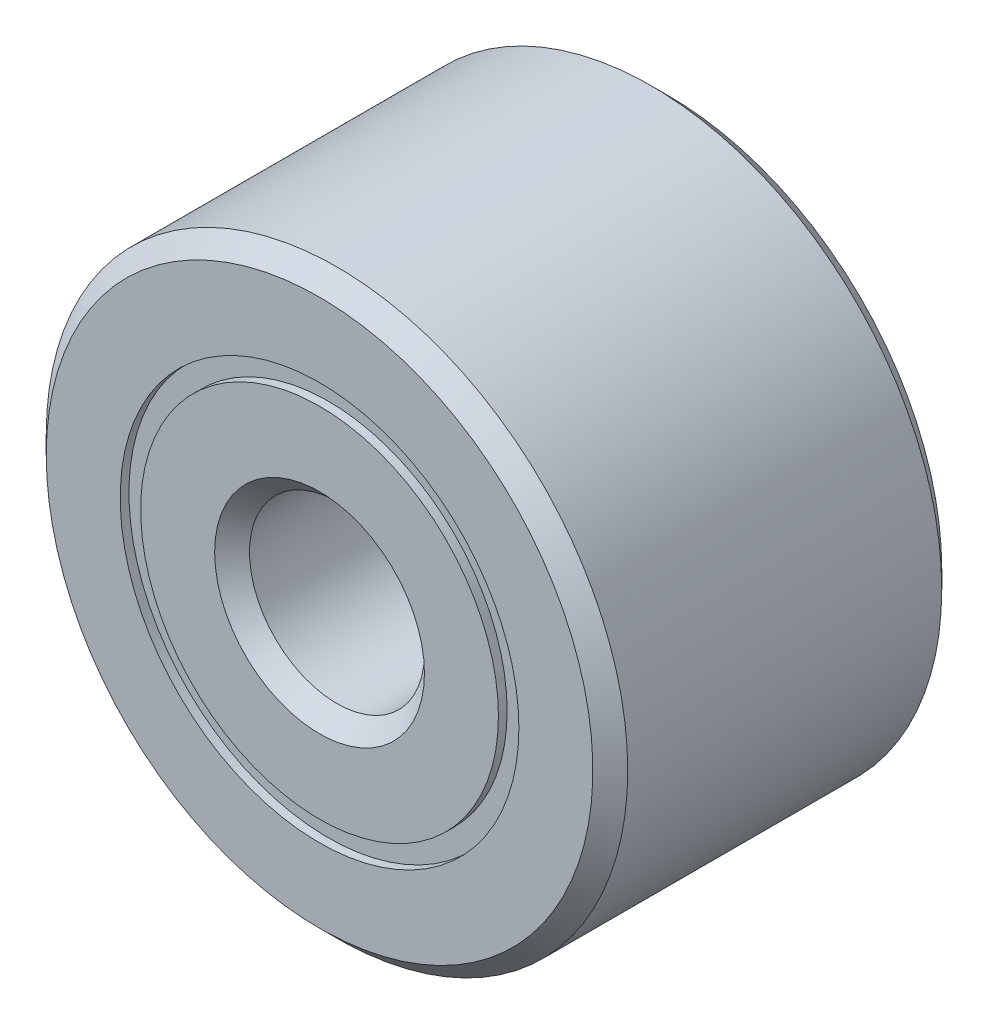
SolidWorks part; units mm, degrees
material "A-Glass Fiber"
ref_plane "Front Plane" through (0, 0, 0) normal (0, 0, 1) x (1, 0, 0)
ref_plane "Top Plane" through (0, 0, 0) normal (0, 1, 0) x (1, 0, 0)
ref_plane "Right Plane" through (0, 0, 0) normal (1, 0, 0) x (0, 0, -1)
sketch "Sketch1" plane through (0, 0, 0) normal (1, 0, 0) x (0, 0, -1)
  line L0 (-1.1906, 0) -> (1.1906, 0) construction
  line L1 (0, 1.9844) -> (0, -1.9844) construction
  line L2 (1.0716, 1.9844) -> (-1.0716, 1.9844)
  line L3 (-1.0716, 1.9844) -> (-1.1906, 1.8653)
  line L4 (-1.1906, 1.8653) -> (-1.1906, 1.3604)
  line L5 (-1.1906, 1.3604) -> (-0.5292, 1.3604)
  line L6 (1.1906, 1.3604) -> (0.5292, 1.3604)
  line L7 (1.1906, 1.8653) -> (1.1906, 1.3604)
  line L8 (1.0716, 1.9844) -> (1.1906, 1.8653)
  line L9 (0, 1.9844) -> (0, 1.2906) construction
  line L10 (0, 1.2906) -> (0, 0.5969) construction
  arc A0 (-0.5292, 1.3604) -> (0.5292, 1.3604) centre (0, 1.2906) cw
  point P14 (0, 0.5969)
  dimension "Width" = 2.3813
  dimension "OD" = 3.9688
  dimension "D1" = 45
  dimension "D2" = 0.1191
  dimension "D3" = 1.0583
  dimension "D4" = 0.0698
revolve "Revolve1" add sketch "Sketch1" angle 360 about L0
sketch "Sketch3" plane through (0, 0, 0) normal (1, 0, 0) x (0, 0, -1)
  line L0 (-0.5292, 1.2209) -> (-1.1906, 1.2209)
  line L1 (-1.1906, 1.8653) -> (-1.1906, 1.3604) construction
  line L2 (-1.0716, 1.9844) -> (-1.1906, 1.8653) construction
  line L3 (-1.1906, 1.2209) -> (-1.1906, 0.716)
  line L5 (-1.1906, 0.716) -> (-1.0716, 0.5969)
  line L6 (-1.0716, 0.5969) -> (1.0716, 0.5969)
  line L7 (1.0716, 1.9844) -> (1.0716, -1.9844) construction
  line L8 (1.0716, 0.5969) -> (1.1906, 0.716)
  line L9 (1.1906, -1.8653) -> (1.1906, 1.8653) construction
  line L10 (1.1906, 0.716) -> (1.1906, 1.2209)
  line L11 (1.1906, 1.2209) -> (0.5292, 1.2209)
  line L12 (0, 1.9844) -> (0, -1.9844) construction
  line L13 (1.0716, 1.9844) -> (1.1906, 1.8653) construction
  arc A1 (0.5292, 1.2209) -> (-0.5292, 1.2209) centre (0, 1.2906) cw
  arc A2 (0.5292, 1.3604) -> (-0.5292, 1.3604) centre (0, 1.2906) ccw construction
revolve "Revolve3" add sketch "Sketch3" angle 360 about L0
sketch "Sketch4" plane through (0, 0, 0) normal (1, 0, 0) x (0, 0, -1)
  line L0 (-0.5337, 1.2906) -> (0.5337, 1.2906)
  arc A2 (-0.5337, 1.2906) -> (0.5337, 1.2906) centre (0, 1.2906) cw
  arc A3 (0.5292, 1.3604) -> (-0.5292, 1.3604) centre (0, 1.2906) ccw construction
revolve "Revolve4" add sketch "Sketch4" angle 360 about L0
ref_axis "Axis1" through (0, 0, -1.1906) along (0, 0, 1)
pattern_circular "CirPattern1" count 6 every 60 about axis through (0, 0, -1.1906) along (0, 0, 1) of bodies 104
sketch "Sketch5" plane through (0, 0, 0) normal (1, 0, 0) x (0, 0, -1)
  line L0 (-1.1906, 1.3604) -> (-0.5292, 1.3604) construction
  line L1 (-1.1311, 1.3604) -> (-0.5337, 1.3604)
  line L2 (-1.1311, 1.3604) -> (-1.1311, 1.2209)
  line L3 (-1.1311, 1.2209) -> (-0.5337, 1.2209)
  line L4 (-0.5337, 1.3604) -> (-0.5337, 1.2209)
  line L5 (-0.5292, 1.2209) -> (-1.1906, 1.2209) construction
  line L6 (1.1906, 1.3604) -> (0.5292, 1.3604) construction
  line L7 (1.1311, 1.3604) -> (0.5337, 1.3604)
  line L8 (1.1311, 1.3604) -> (1.1311, 1.2209)
  line L9 (1.1311, 1.2209) -> (0.5337, 1.2209)
  line L10 (0.5337, 1.3604) -> (0.5337, 1.2209)
  line L11 (1.1906, 1.2209) -> (0.5292, 1.2209) construction
  line L12 (-1.0716, 1.9844) -> (-1.1906, 1.8653) construction
  point P18 (-1.1311, 1.9248)
revolve "Revolve5" add sketch "Sketch5" angle 360 about L0
equation "\"D2@Sketch1\" = \"Width@Sketch1\"*.05"
equation "\"D3@Sketch1\" = \"Width@Sketch1\"/2.25"
equation "\"D4@Sketch1\" = (((\"OD@Sketch1\"-\"Width@Sketch1\")/2)/3.25)/3.5"
equation "\"D2@CirPattern1\" = 360/\"Balls@CirPattern1\""
